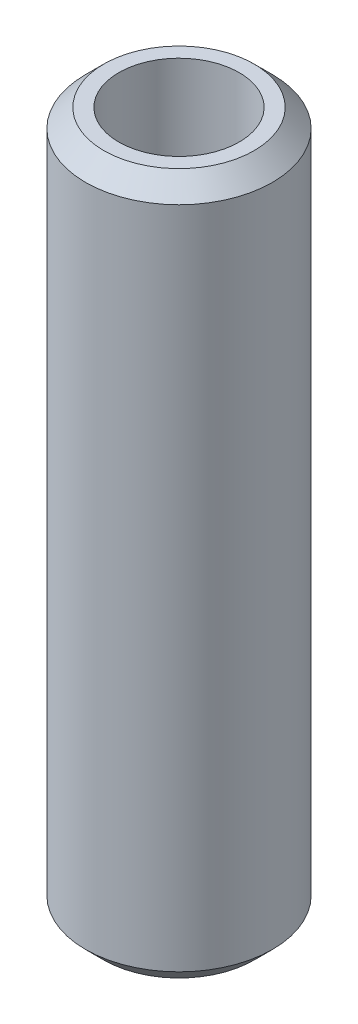
SolidWorks part; units mm, degrees
ref_plane "Front Plane" through (0, 0, 0) normal (0, 0, 1) x (1, 0, 0)
ref_plane "Top Plane" through (0, 0, 0) normal (0, 1, 0) x (1, 0, 0)
ref_plane "Right Plane" through (0, 0, 0) normal (1, 0, 0) x (0, 0, -1)
sketch "Sketch1" plane through (0, 0, 0) normal (0, 1, 0) x (1, 0, 0)
  circle A0 centre (0, 0) radius 12.5
  dimension "SHAFT_OD" = 25
extrude "Boss-Extrude1" add sketch "Sketch1" along normal blind 93.7682
sketch "Sketch2" plane through (0, 0, 0) normal (0, 1, 0) x (1, 0, 0)
  circle A0 centre (0, 0) radius 8.054
  dimension "BORE_D" = 16.1081
extrude "Cut-Extrude1" cut sketch "Sketch2" along normal through all
chamfer "Chamfer1" distance 2.4515 angle 45 2 edges at (0, 93.7682, 12.5) (0, 0, 12.5)
